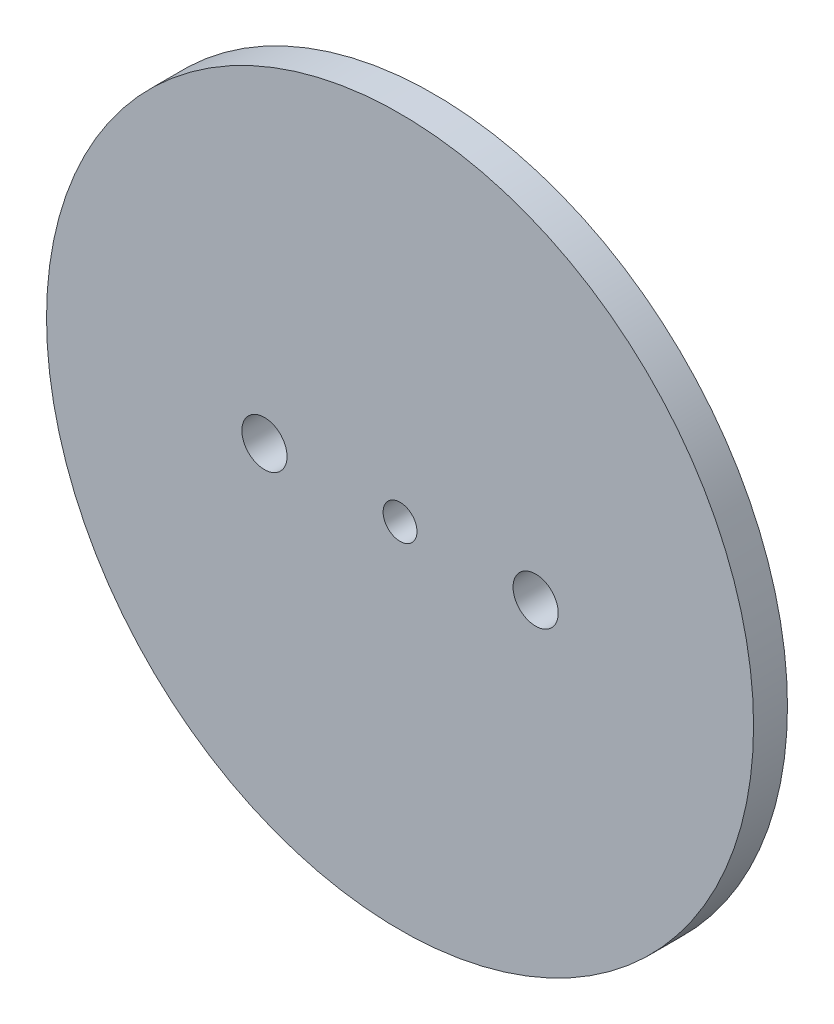
SolidWorks part; units mm, degrees
material "E-Glass Fiber"
ref_plane "Front Plane" through (0, 0, 0) normal (0, 0, 1) x (1, 0, 0)
ref_plane "Top Plane" through (0, 0, 0) normal (0, 1, 0) x (1, 0, 0)
ref_plane "Right Plane" through (0, 0, 0) normal (1, 0, 0) x (0, 0, -1)
sketch "Sketch1" plane through (0, 0, 0) normal (0, 0, 1) x (1, 0, 0)
  circle A0 centre (0, 0) radius 49.6697
  dimension "D1" = 99.3394
extrude "Boss-Extrude1" add sketch "Sketch1" along normal blind 4.7625
sketch "Sketch2" plane through (0, 0, 4.7625) normal (0, 0, 1) x (1, 0, 0)
  line L0 (19.05, 0) -> (0, 0) construction
  line L1 (0, 0) -> (-19.05, 0) construction
  circle A0 centre (0, 0) radius 2.3812
  circle A1 centre (19.05, 0) radius 3.175
  circle A2 centre (-19.05, 0) radius 3.175
  dimension "D1" = 4.7625
  dimension "D2" = 6.35
  dimension "D3" = 19.05
extrude "Cut-Extrude1" cut sketch "Sketch2" against normal through all
